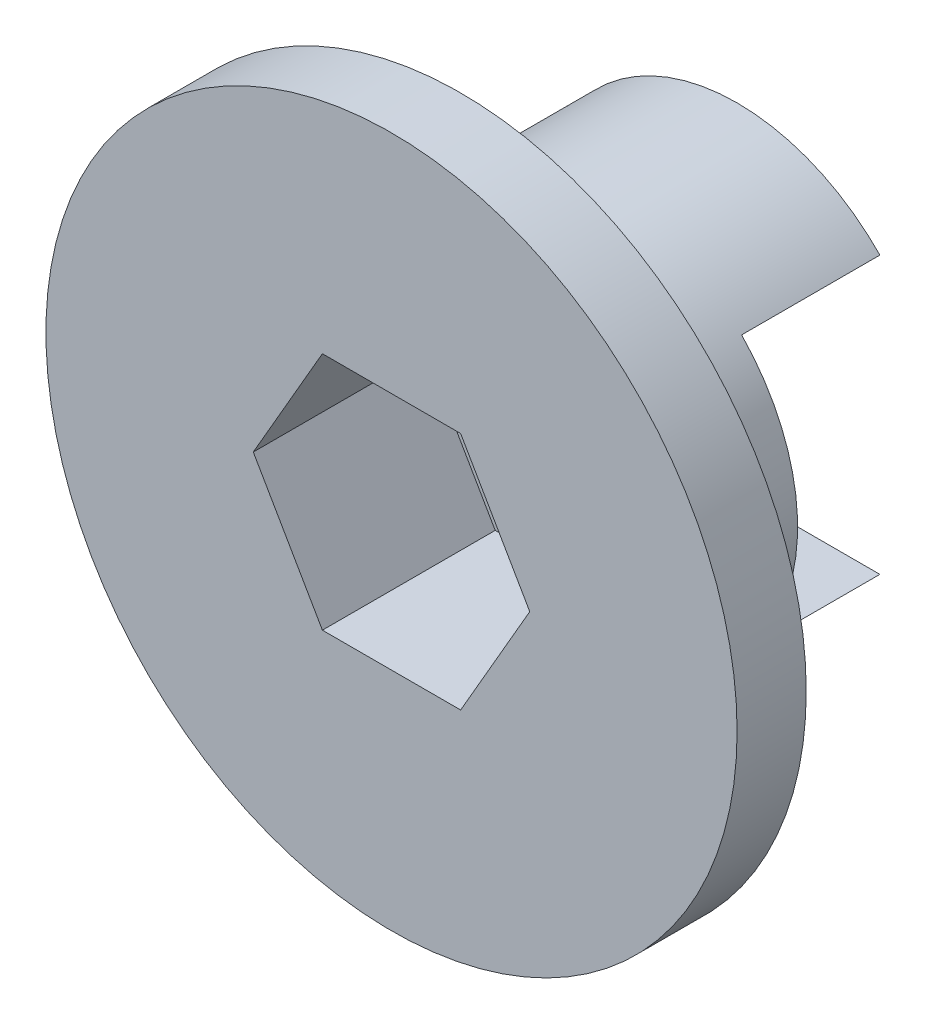
SolidWorks part; units mm, degrees
ref_plane "Front Plane" through (0, 0, 0) normal (0, 0, 1) x (1, 0, 0)
ref_plane "Top Plane" through (0, 0, 0) normal (0, 1, 0) x (1, 0, 0)
ref_plane "Right Plane" through (0, 0, 0) normal (1, 0, 0) x (0, 0, -1)
sketch "Sketch1" plane through (0, 0, 0) normal (0, 0, 1) x (1, 0, 0)
  circle A0 centre (0, 0) radius 11.5
  circle A1 centre (0, 0) radius 5
  dimension "D1" = 23
  dimension "D2" = 10
extrude "Boss-Extrude1" add sketch "Sketch1" along normal blind 20
sketch "Sketch2" plane through (0, 0, 20) normal (0, 0, 1) x (1, 0, 0)
  line L1 (8, 0) -> (4, 6.9282)
  line L2 (4, 6.9282) -> (-4, 6.9282)
  line L3 (-4, 6.9282) -> (-8, 0)
  line L4 (-8, 0) -> (-4, -6.9282)
  line L5 (-4, -6.9282) -> (4, -6.9282)
  line L6 (4, -6.9282) -> (8, 0)
  circle A0 centre (0, 0) radius 6.9282 construction
  dimension "D1" = 16
extrude "Cut-Extrude1" cut sketch "Sketch2" against normal blind 10
sketch "Sketch3" plane through (0, 0, 0) normal (1, 0, 0) x (0, 0, -1)
  line L0 (0, -11.5) -> (0, 11.5) construction
  line L1 (0, 8) -> (-8, 8)
  line L2 (0, 8) -> (0, -8)
  line L3 (0, -8) -> (-8, -8)
  line L4 (-8, 8) -> (-8, -8)
  point P6 (-8, 0)
  dimension "D1" = 16
  dimension "D2" = 8
extrude "Cut-Extrude2" cut sketch "Sketch3" against normal through all and the other way through all
sketch "Sketch4" plane through (0, 0, 20) normal (0, 0, 1) x (1, 0, 0)
  circle A0 centre (0, 0) radius 11.5 construction
  circle A1 centre (0, 0) radius 11.5
  circle A2 centre (0, 0) radius 20
  dimension "D1" = 40
extrude "Boss-Extrude2" add sketch "Sketch4" against normal blind 4
